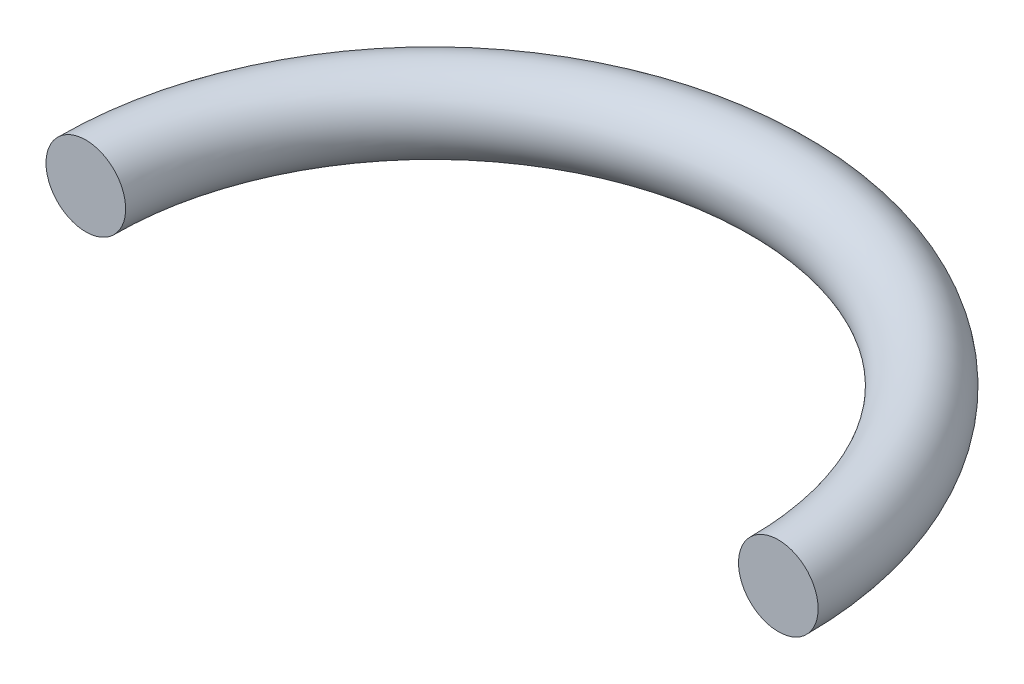
SolidWorks part; units mm, degrees
ref_plane "Front Plane" through (0, 0, 0) normal (0, 0, 1) x (1, 0, 0)
ref_plane "Top Plane" through (0, 0, 0) normal (0, 1, 0) x (1, 0, 0)
ref_plane "Right Plane" through (0, 0, 0) normal (1, 0, 0) x (0, 0, -1)
sketch "Sketch1" plane through (0, 0, 0) normal (0, 1, 0) x (1, 0, 0)
  line L0 (-127, 0) -> (127, 0) construction
  arc A0 (127, 0) -> (-127, 0) centre (0, 0) ccw
  dimension "D1" = 127
sketch "Sketch2" plane through (0, 0, 0) normal (0, 0, 1) x (1, 0, 0)
  circle A0 centre (127, 0) radius 14.605
  dimension "D1" = 29.21
sweep "Sweep1" add profiles "Sketch2" path "Sketch1"
ref_point "Point1"
ref_point "Point2"
ref_axis "Axis1" through (-127, 0, 0) along (0, 0, 1)
ref_axis "Axis2" through (127, 0, 0) along (0, 0, 1)
ref_plane "Plane1" through (0, 0, 0) normal (0, -1, 0) x (-1, 0, 0)
